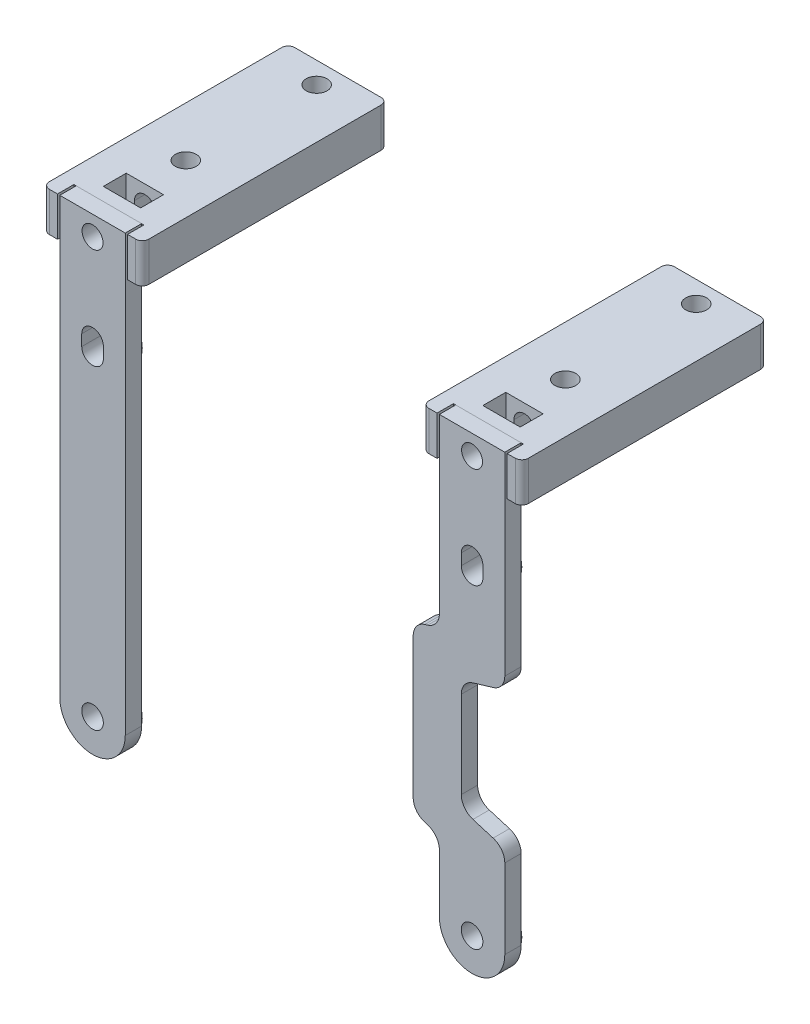
SolidWorks part; units mm, degrees
ref_plane "Front Plane" through (0, 0, 0) normal (0, 0, 1) x (1, 0, 0)
ref_plane "Top Plane" through (0, 0, 0) normal (0, 1, 0) x (1, 0, 0)
ref_plane "Right Plane" through (0, 0, 0) normal (1, 0, 0) x (0, 0, -1)
sketch "Sketch2" plane through (0, 0, 0) normal (0, 0, 1) x (1, 0, 0)
  circle A0 centre (-20, 25) radius 4
  circle A1 centre (38, 25) radius 4
  circle A2 centre (38, -24) radius 4
  circle A3 centre (-20, -24) radius 4
  circle A4 centre (-20, 25) radius 1.65
  circle A5 centre (38, 25) radius 1.65
  circle A6 centre (38, -24) radius 1.65
  circle A7 centre (-20, -24) radius 1.65
  dimension "D1" = 8
  dimension "D2" = 3.3
extrude "Boss-Extrude1" add sketch "Sketch2" along normal blind 1.1
sketch "Sketch3" plane through (0, 0, 1.1) normal (0, 0, 1) x (1, 0, 0)
  circle A0 centre (38, 25) radius 5
  circle A1 centre (38, -24) radius 5
  circle A2 centre (-20, -24) radius 5
  circle A3 centre (-20, 25) radius 5
  circle A4 centre (38, -24) radius 1.65 construction
  circle A5 centre (38, -24) radius 1.65
  circle A6 centre (-20, -24) radius 1.65 construction
  circle A7 centre (-20, -24) radius 1.65
  circle A8 centre (-20, 25) radius 1.65 construction
  circle A9 centre (-20, 25) radius 1.65
  circle A10 centre (38, 25) radius 1.65 construction
  circle A11 centre (38, 25) radius 1.65
  dimension "D1" = 10
extrude "Boss-Extrude2" add sketch "Sketch3" along normal blind 2.5
sketch "Sketch5" plane through (0, 0, 3.6) normal (0, 0, 1) x (1, 0, 0)
  line L0 (43, -24) -> (43, 25)
  line L1 (33, -24) -> (33, 25)
  line L2 (-15, -24) -> (-15, 25)
  line L3 (-25, -24) -> (-25, 25)
  line L4 (36.35, -24) -> (36.35, 25)
  line L5 (43, 0.5) -> (-25, 0.5) construction
  line L6 (43, -10) -> (36.35, -8)
  line L7 (43, 11) -> (36.35, 9)
  line L8 (36.35, -8) -> (43, 0.5) construction
  line L9 (43, 0.5) -> (36.35, 9) construction
  line L10 (43, -10) -> (36.35, 0.5) construction
  line L11 (36.35, 0.5) -> (43, 11) construction
  line L12 (43, -24) -> (36.35, -24) construction
  line L13 (36.35, -24) -> (33, -24) construction
  line L14 (33, -24) -> (28.6174, -24) construction
  line L15 (33, -13.258) -> (29, -12.055)
  line L16 (29, -12.055) -> (29, 13.055)
  line L17 (29, 13.055) -> (33, 14.258)
  line L18 (-15, -24) -> (-25, -24) construction
  line L19 (-15, 25) -> (-25, 25) construction
  line L20 (43, 25) -> (33, 25) construction
  line L21 (43, 25) -> (43, 42.5)
  line L22 (43, 42.5) -> (33, 42.5)
  line L23 (33, 42.5) -> (33, 25)
  line L24 (-15, 25) -> (-15, 42.5)
  line L25 (-15, 42.5) -> (-25, 42.5)
  line L26 (-25, 42.5) -> (-25, 25)
  line L27 (33, 42.5) -> (-15, 42.5) construction
  line L28 (43, 36.5) -> (-25, 36.5) construction
  circle A0 centre (38, -24) radius 5 construction
  circle A1 centre (38, 25) radius 5 construction
  circle A2 centre (-20, -24) radius 5 construction
  circle A3 centre (-20, 25) radius 5 construction
  circle A4 centre (38, -24) radius 1.65 construction
  circle A5 centre (38, 25) radius 1.65 construction
  circle A7 centre (-20, -24) radius 5
  circle A8 centre (-20, -24) radius 5
  circle A9 centre (-20, 25) radius 5
  circle A10 centre (-20, 25) radius 5
  circle A11 centre (38, -24) radius 5
  circle A12 centre (38, -24) radius 5
  circle A13 centre (38, 25) radius 5
  circle A14 centre (38, 25) radius 5
  point P31 (29, 0.5)
  circle M23 centre (38, -24) radius 5
  dimension "D1" = 17
  dimension "D2" = 21
  dimension "D3" = 6
  dimension "D4" = 4
  dimension "D5" = 7.35
  dimension "D6" = 73.261
  dimension "D7" = 6
  dimension "D8" = 36
  dimension "D9" = 0
  dimension "D10" = 0
  dimension "D11" = 0
  dimension "D12" = 0
extrude "Boss-Extrude3" add sketch "Sketch5" against normal blind 2.5 contours A10 L3 A8 L2 | A10 L24 L25 L26 | L0 L6 L4 M23 | A14 L1 L4 M23 | L17 L16 L15 L1 | A14 L4 L7 L0 | A14 L21 L22 L23 region at (39.731, -14.451, 3.6) region at (34.628, 0.5, 3.6) region at (39.731, 15.451, 3.6) region at (31.0305, 0.5, 3.6) region at (38, 35.6676, 3.6) region at (-20, 0.5, 3.6) region at (-20, 35.6676, 3.6)
fillet "Fillet1" radius 2.5 8 edges at (43, 11, 2.35) (43, -10, 2.35) (36.35, -8, 2.35) (36.35, 9, 2.35) (33, 14.258, 2.35) (29, 13.055, 2.35) (29, -12.055, 2.35) (33, -13.258, 2.35)
sketch "Sketch6" plane through (0, 0, 1.1) normal (0, 0, -1) x (-1, 0, 0)
  line L10 (-43, 42.5) -> (-33, 42.5) construction
  line L11 (-45.6, 42.5) -> (27.6, 42.5)
  line L12 (-45.6, 42.5) -> (-45.6, 36.5)
  line L13 (-45.6, 36.5) -> (27.6, 36.5)
  line L14 (27.6, 42.5) -> (27.6, 36.5)
  line L15 (-43, 12.8587) -> (-43, 42.5) construction
  line L16 (25, -24) -> (25, 42.5) construction
  line L17 (-33, 16.1167) -> (-33, 42.5) construction
  line L18 (-30.4, 42.5) -> (12.4, 42.5)
  line L19 (-30.4, 42.5) -> (-30.4, 36.5)
  line L20 (-30.4, 36.5) -> (12.4, 36.5)
  line L21 (12.4, 42.5) -> (12.4, 36.5)
  line L22 (15, -24) -> (15, 42.5) construction
  point P9 (-45.6, 39.5)
  line M7 (25, -24) -> (25, 42.5)
  line M8 (25, 42.5) -> (15, 42.5)
  line M9 (15, 42.5) -> (15, -24)
  dimension "D1" = 2.6
  dimension "D2" = 2.6
  dimension "D3" = 6
  dimension "D4" = 2.6
  dimension "D5" = 2.6
extrude "Boss-Extrude4" add sketch "Sketch6" along normal blind 35 separate body contours L19 L11 L12 L13 | L13 M9 M7 M8 | L11 L21 L13 M9 | L14 L11 L13 M7 region at (38, 39.5, 1.1) region at (-13.7, 39.5, 1.1) region at (-20, 39.5, 1.1) region at (-26.3, 39.5, 1.1)
sketch "Sketch7" plane through (0, 0, 3.6) normal (0, 0, 1) x (1, 0, 0)
  line L0 (38, 25.85) -> (38, 24.15) construction
  line L1 (39.65, 25.85) -> (39.65, 24.15)
  line L2 (36.35, 25.85) -> (36.35, 24.15)
  line L3 (-20, 25.85) -> (-20, 24.15) construction
  line L4 (-18.35, 25.85) -> (-18.35, 24.15)
  line L5 (-21.65, 25.85) -> (-21.65, 24.15)
  line L6 (-20, 25.85) -> (38, 25.85) construction
  arc A0 (39.65, 25.85) -> (36.35, 25.85) centre (38, 25.85) ccw
  arc A1 (36.35, 24.15) -> (39.65, 24.15) centre (38, 24.15) ccw
  arc A2 (-18.35, 25.85) -> (-21.65, 25.85) centre (-20, 25.85) ccw
  arc A3 (-21.65, 24.15) -> (-18.35, 24.15) centre (-20, 24.15) ccw
  circle A4 centre (-20, 25) radius 1.65 construction
  circle A5 centre (38, 25) radius 1.65 construction
  point P2 (38, 25)
  point P9 (-20, 25)
  dimension "D1" = 5
extrude "Cut-Extrude1" cut sketch "Sketch7" against normal through all
sketch "Sketch8" plane through (0, 0, 3.6) normal (0, 0, 1) x (1, 0, 0)
  line L0 (-27.6, 39.5) -> (45.6, 39.5) construction
  line L1 (-27.6, 42.5) -> (-27.6, 36.5) construction
  line L2 (45.6, 42.5) -> (45.6, 36.5) construction
  line L3 (-20, 42.5) -> (-20, 39.5) construction
  line L4 (-15, 42.5) -> (-25, 42.5) construction
  line L5 (38, 42.5) -> (38, 39.5) construction
  line L6 (43, 42.5) -> (33, 42.5) construction
  circle A0 centre (-20, 39.5) radius 1.6
  circle A1 centre (38, 39.5) radius 1.6
  dimension "D1" = 3.2
extrude "Cut-Extrude2" cut sketch "Sketch8" against normal blind 10.5
sketch "Sketch9" plane through (0, 0, 1.1) normal (0, 0, 1) x (1, 0, 0)
  line L0 (45.6, 36.5) -> (30.4, 36.5) construction
  line L1 (45.6, 42.5) -> (43.35, 42.5)
  line L2 (45.6, 42.5) -> (45.6, 36.5)
  line L3 (45.6, 36.5) -> (43.35, 36.5)
  line L4 (43.35, 42.5) -> (43.35, 36.5)
  line L5 (-12.4, 36.5) -> (-27.6, 36.5) construction
  line L6 (30.4, 42.5) -> (32.65, 42.5)
  line L7 (30.4, 42.5) -> (30.4, 36.5)
  line L8 (30.4, 36.5) -> (32.65, 36.5)
  line L9 (32.65, 42.5) -> (32.65, 36.5)
  line L10 (-12.4, 42.5) -> (-14.65, 42.5)
  line L11 (-12.4, 42.5) -> (-12.4, 36.5)
  line L12 (-12.4, 36.5) -> (-14.65, 36.5)
  line L13 (-14.65, 42.5) -> (-14.65, 36.5)
  line L14 (33, 16.1167) -> (33, 42.5) construction
  line L15 (-27.6, 42.5) -> (-25.35, 42.5)
  line L16 (-27.6, 42.5) -> (-27.6, 36.5)
  line L17 (-27.6, 36.5) -> (-25.35, 36.5)
  line L18 (-25.35, 42.5) -> (-25.35, 36.5)
  point P24 (31.525, 42.5)
  dimension "D1" = 0.35
extrude "Boss-Extrude5" add sketch "Sketch9" along normal blind 2.5 separate body
combine bodies "Combine1" operation type add bodies to combine 122 120 116
combine bodies "Combine2" operation type add bodies to combine 121 119 115
sketch "Sketch10" plane through (0, 0, 1.1) normal (0, 0, 1) x (1, 0, 0)
  line L0 (36.4, 39.5) -> (36.4, 37.9)
  line L1 (36.4, 37.9) -> (38, 37.9)
  line L2 (38, 37.9) -> (39.6, 37.9)
  line L3 (39.6, 37.9) -> (39.6, 39.5)
  line L4 (-21.6, 39.5) -> (-21.6, 37.9)
  line L5 (-21.6, 37.9) -> (-20, 37.9)
  line L6 (-20, 37.9) -> (-18.4, 37.9)
  line L7 (-18.4, 37.9) -> (-18.4, 39.5)
  circle A0 centre (38, 39.5) radius 1.6 construction
  circle A1 centre (38, 39.5) radius 1.6 construction
  circle A2 centre (38, 39.5) radius 1.6
  circle A3 centre (-20, 39.5) radius 1.6 construction
  circle A4 centre (-20, 39.5) radius 1.6
  point P18 (36.4, 37.9)
  point P19 (38, 37.9)
  point P20 (39.6, 39.5)
  point P21 (36.4, 39.5)
  circle M6 centre (38, 39.5) radius 1.6
extrude "Cut-Extrude4" cut sketch "Sketch10" against normal up to surface (8 mm away) contours L2 L3 M6 | L0 L1 M6 | A4 L6 L7 | A4 L4 L5 | M6 | A4 region at (36.7574, 38.2574, 1.1) region at (38, 39.5, 1.1) region at (39.2426, 38.2574, 1.1) region at (-21.2426, 38.2574, 1.1) region at (-20, 39.5, 1.1) region at (-18.7574, 38.2574, 1.1) up to face at (-18.4, 39.5, -6.9)
sketch "Sketch11" plane through (0, 36.5, 0) normal (0, -1, 0) x (1, 0, 0)
  line L0 (-20, 1.1) -> (-20, -33.9) construction
  line L1 (-14.65, 1.1) -> (-25.35, 1.1) construction
  line L2 (-12.4, -33.9) -> (-27.6, -33.9) construction
  line L3 (38, 1.1) -> (38, -33.9) construction
  line L4 (43.35, 1.1) -> (32.65, 1.1) construction
  line L5 (45.6, -33.9) -> (30.4, -33.9) construction
  line L6 (-20, -2.65) -> (38, -2.65) construction
  line L7 (-22.85, -0.9) -> (-17.15, -0.9)
  line L8 (-22.85, -0.9) -> (-22.85, -4.4)
  line L9 (-22.85, -4.4) -> (-17.15, -4.4)
  line L10 (-17.15, -0.9) -> (-17.15, -4.4)
  line L11 (-22.85, -0.9) -> (-17.15, -4.4) construction
  line L12 (-22.85, -4.4) -> (-17.15, -0.9) construction
  line L13 (35.15, -0.9) -> (40.85, -0.9)
  line L14 (35.15, -0.9) -> (35.15, -4.4)
  line L15 (35.15, -4.4) -> (40.85, -4.4)
  line L16 (40.85, -0.9) -> (40.85, -4.4)
  line L17 (35.15, -0.9) -> (40.85, -4.4) construction
  line L18 (35.15, -4.4) -> (40.85, -0.9) construction
  line L19 (-20, -10.65) -> (38, -10.65) construction
  line L20 (-20, -30.65) -> (38, -30.65) construction
  line L21 (-23.25, -30.65) -> (-23.25, -33.9)
  line L22 (-23.25, -33.9) -> (-16.75, -33.9)
  line L23 (-16.75, -33.9) -> (-16.75, -30.65)
  line L24 (34.75, -30.65) -> (34.75, -33.9)
  line L25 (34.75, -33.9) -> (41.25, -33.9)
  line L26 (41.25, -33.9) -> (41.25, -30.65)
  circle A0 centre (-20, -10.65) radius 1.6
  circle A1 centre (-20, -30.65) radius 1.6
  circle A2 centre (38, -10.65) radius 1.6
  circle A3 centre (38, -30.65) radius 1.6
  circle A4 centre (-20, -10.65) radius 3.25
  circle A5 centre (38, -10.65) radius 3.25
  circle A6 centre (38, -30.65) radius 3.25
  circle A7 centre (-20, -30.65) radius 3.25
  point P12 (-20, -2.65)
  point P17 (38, -2.65)
  line M16 (30.4, -33.9) -> (45.6, -33.9)
  dimension "D1" = 3.2
  dimension "D2" = 6.5
  dimension "D3" = 5.7
  dimension "D4" = 2
  dimension "D5" = 3.5
  dimension "D6" = 20
extrude "Cut-Extrude5" cut sketch "Sketch11" against normal through all contours L16 L13 L14 L15 | A2 | A3 | L10 L7 L8 L9 | A0 | A1 region at (-20, 36.5, -2.65) region at (38, 36.5, -2.65) region at (-20, 36.5, -10.65) region at (-20, 36.5, -30.65) region at (38, 36.5, -10.65) region at (38, 36.5, -30.65)
extrude "Cut-Extrude6" cut sketch "Sketch11<3>" against normal blind 2.5 contours A4 A0 | A7 A1 | A7 L21 L22 | A7 L22 L23 | A5 A2 | A6 A3 | A6 L24 M16 | A6 L25 L26 region at (-22.5241, 36.5, -33.1741) region at (-20, 36.5, -27.4919) region at (-17.4759, 36.5, -33.1741) region at (35.4759, 36.5, -33.1741) region at (38, 36.5, -27.4919) region at (40.5241, 36.5, -33.1741) region at (-23.1581, 36.5, -10.65) region at (34.8419, 36.5, -10.65)
sketch "Sketch11<3>" plane through (0, 36.5, 0) normal (0, -1, 0) x (1, 0, 0) same geometry as "Sketch11"
fillet "Fillet2" radius 1 6 edges at (-12.4, 39.5, -33.9) (-27.6, 39.5, -33.9) (-23.25, 37.75, -33.9) (-16.75, 37.75, -33.9) (-27.6, 39.5, 3.6) (-12.4, 39.5, 3.6)
fillet "Fillet3" radius 1 6 edges at (45.6, 39.5, 3.6) (30.4, 39.5, 3.6) (45.6, 39.5, -33.9) (41.25, 37.75, -33.9) (34.75, 37.75, -33.9) (30.4, 39.5, -33.9)
